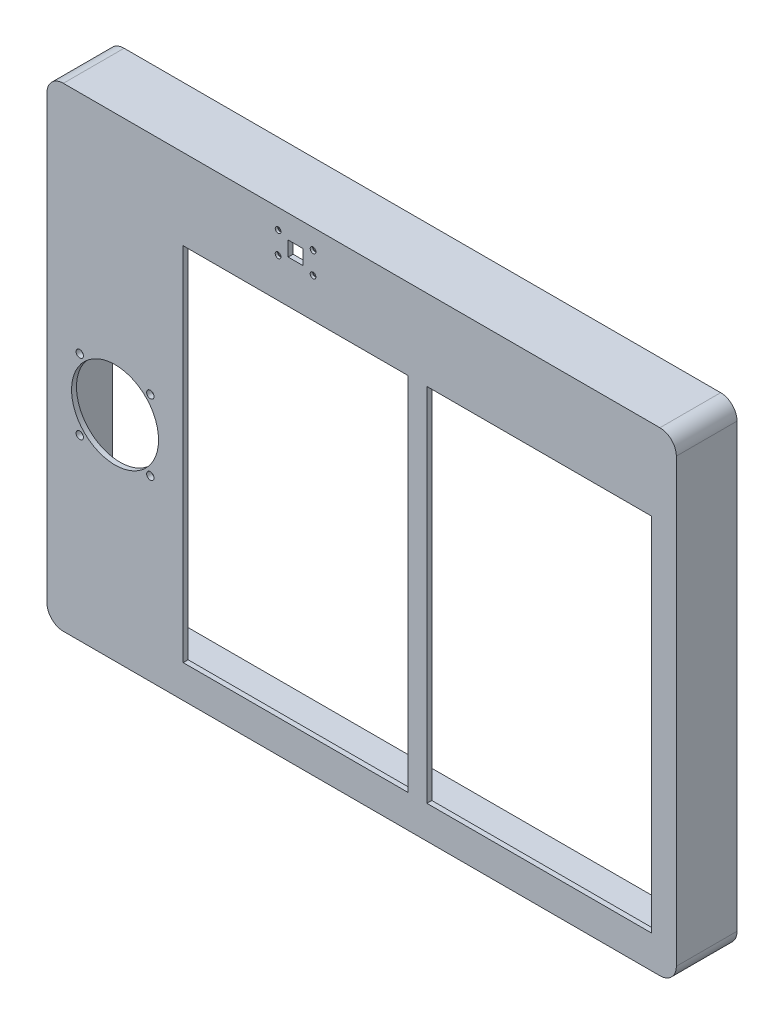
SolidWorks part; units mm, degrees
ref_plane "前视基准面" through (0, 0, 0) normal (0, 0, 1) x (1, 0, 0)
ref_plane "上视基准面" through (0, 0, 0) normal (0, 1, 0) x (1, 0, 0)
ref_plane "右视基准面" through (0, 0, 0) normal (1, 0, 0) x (0, 0, -1)
other "Configuration Table"
sketch "草图1" plane through (0, 0, 0) normal (0, 0, 1) x (1, 0, 0)
  line L0 (151.5, 0) -> (292.5, 0)
  line L1 (3, 0) -> (144, 0)
  line L2 (0, -3) -> (0, -237)
  line L3 (3, -240) -> (144, -240)
  line L4 (147, -3) -> (147, -237)
  line L5 (31.5, -60) -> (115.5, -60)
  line L6 (28.5, -63) -> (28.5, -177)
  line L7 (31.5, -180) -> (115.5, -180)
  line L8 (118.5, -63) -> (118.5, -177)
  line L9 (148.5, -3) -> (148.5, -237)
  line L10 (151.5, -240) -> (292.5, -240)
  line L11 (295.5, -3) -> (295.5, -237)
  line L12 (180, -60) -> (264, -60)
  line L13 (177, -63) -> (177, -177)
  line L14 (180, -180) -> (264, -180)
  line L15 (267, -63) -> (267, -177)
  line L17 (5, -10) -> (142, -10)
  line L18 (-65, -151.5) -> (-8, -151.5)
  line L19 (-68, -148.5) -> (-68, -91.5)
  line L20 (-65, -88.5) -> (-8, -88.5)
  line L21 (-5, -148.5) -> (-5, -91.5)
  line L22 (-68, -151.5) -> (-5, -88.5) construction
  line L23 (-68, -88.5) -> (-5, -151.5) construction
  line L24 (5, -10) -> (5, -230)
  line L25 (-68, 39.2) -> (295.5, 39.2)
  line L26 (-78, 29.2) -> (-78, -240)
  line L27 (-68, -250) -> (295.5, -250)
  line L28 (305.5, 29.2) -> (305.5, -240)
  line L29 (5, -230) -> (142, -230)
  line L30 (142, -10) -> (142, -230)
  line L31 (153.5, -10) -> (290.5, -10)
  line L32 (153.5, -10) -> (153.5, -230)
  line L33 (153.5, -230) -> (290.5, -230)
  line L34 (290.5, -10) -> (290.5, -230)
  line L42 (61.85, 29.2) -> (85.15, 29.2)
  line L43 (60.85, 28.2) -> (60.85, 6)
  line L44 (61.85, 5) -> (85.15, 5)
  line L45 (86.15, 28.2) -> (86.15, 6)
  line L46 (69, 25) -> (78, 25)
  line L47 (69, 25) -> (69, 16)
  line L48 (69, 16) -> (78, 16)
  line L49 (78, 25) -> (78, 16)
  circle A0 centre (6.75, -12.5) radius 1.5
  circle A1 centre (140.25, -12.5) radius 1.5
  circle A2 centre (140.25, -231) radius 1.5
  circle A3 centre (6.75, -231) radius 1.5
  arc A4 (0, -237) -> (3, -240) centre (3, -237) ccw
  arc A5 (144, -240) -> (147, -237) centre (144, -237) ccw
  arc A6 (144, 0) -> (147, -3) centre (144, -3) cw
  arc A7 (3, 0) -> (0, -3) centre (3, -3) ccw
  circle A8 centre (6.75, -12.5) radius 2.25
  circle A9 centre (140.25, -12.5) radius 2.25
  circle A10 centre (140.25, -231) radius 2.25
  circle A11 centre (6.75, -231) radius 2.25
  arc A12 (28.5, -177) -> (31.5, -180) centre (31.5, -177) ccw
  arc A13 (115.5, -180) -> (118.5, -177) centre (115.5, -177) ccw
  arc A14 (115.5, -60) -> (118.5, -63) centre (115.5, -63) cw
  arc A15 (31.5, -60) -> (28.5, -63) centre (31.5, -63) ccw
  circle A16 centre (155.25, -12.5) radius 1.5
  circle A17 centre (288.75, -12.5) radius 1.5
  circle A18 centre (288.75, -231) radius 1.5
  circle A19 centre (155.25, -231) radius 1.5
  arc A20 (148.5, -237) -> (151.5, -240) centre (151.5, -237) ccw
  arc A21 (292.5, -240) -> (295.5, -237) centre (292.5, -237) ccw
  arc A22 (292.5, 0) -> (295.5, -3) centre (292.5, -3) cw
  arc A23 (151.5, 0) -> (148.5, -3) centre (151.5, -3) ccw
  circle A24 centre (155.25, -12.5) radius 2.25
  circle A25 centre (288.75, -12.5) radius 2.25
  circle A26 centre (288.75, -231) radius 2.25
  circle A27 centre (155.25, -231) radius 2.25
  arc A28 (177, -177) -> (180, -180) centre (180, -177) ccw
  arc A29 (264, -180) -> (267, -177) centre (264, -177) ccw
  arc A30 (264, -60) -> (267, -63) centre (264, -63) cw
  arc A31 (180, -60) -> (177, -63) centre (180, -63) ccw
  circle A32 centre (-58, -98.5) radius 2.25
  circle A36 centre (-36.5, -120) radius 26.5
  arc A37 (-65, -151.5) -> (-68, -148.5) centre (-65, -148.5) cw
  arc A38 (-8, -151.5) -> (-5, -148.5) centre (-8, -148.5) ccw
  arc A39 (-8, -88.5) -> (-5, -91.5) centre (-8, -91.5) cw
  arc A40 (-68, -91.5) -> (-65, -88.5) centre (-65, -91.5) cw
  circle A41 centre (-15, -98.5) radius 2.25
  circle A42 centre (-15, -141.5) radius 2.25
  circle A43 centre (-58, -141.5) radius 2.25
  arc A44 (295.5, 39.2) -> (305.5, 29.2) centre (295.5, 29.2) cw
  arc A45 (295.5, -250) -> (305.5, -240) centre (295.5, -240) ccw
  arc A46 (-78, -240) -> (-68, -250) centre (-68, -240) ccw
  arc A47 (-68, 39.2) -> (-78, 29.2) centre (-68, 29.2) ccw
  circle A60 centre (62.85, 27.2) radius 1.25
  circle A61 centre (84.15, 27.2) radius 1.25
  circle A62 centre (84.15, 13.9) radius 1.25
  circle A63 centre (62.85, 13.9) radius 1.25
  arc A64 (61.85, 29.2) -> (60.85, 28.2) centre (61.85, 28.2) ccw
  arc A65 (85.15, 29.2) -> (86.15, 28.2) centre (85.15, 28.2) cw
  arc A66 (85.15, 5) -> (86.15, 6) centre (85.15, 6) ccw
  arc A67 (60.85, 6) -> (61.85, 5) centre (61.85, 6) ccw
  circle A68 centre (62.85, 27.2) radius 1.75
  circle A69 centre (84.15, 27.2) radius 1.75
  circle A70 centre (84.15, 13.9) radius 1.75
  circle A71 centre (62.85, 13.9) radius 1.75
  point P23 (0, 0)
  point P33 (-36.5, -120)
  point P38 (118.5, -180)
  point P41 (118.5, -60)
  point P44 (28.5, -60)
  dimension "D1" = 3
  dimension "D10" = 3
  dimension "D11" = 4.5
  dimension "D18" = 3
  dimension "D9" = 3
  dimension "D22" = 3
  dimension "D23" = 4.5
  dimension "D26" = 3
  dimension "D33" = 4.5
  dimension "D40" = 53
  dimension "D41" = 3
  dimension "D50" = 10
  dimension "D59" = 13.3
  dimension "D69" = 60.85
  dimension "D46" = 21.3
  dimension "D68" = 10
  dimension "D4" = 147
  dimension "D5" = 240
  dimension "D6" = 133.5
  dimension "D7" = 6.75
  dimension "D8" = 218.5
  dimension "D14" = 90
  dimension "D15" = 120
  dimension "D16" = 28.5
  dimension "D17" = 60
  dimension "D19" = 12.5
  dimension "D20" = 133.5
  dimension "D21" = 218.5
  dimension "D24" = 28.5
  dimension "D25" = 60
  dimension "D27" = 147
  dimension "D28" = 6.75
  dimension "D29" = 240
  dimension "D30" = 12.5
  dimension "D31" = 15
  dimension "D32" = 133.5
  dimension "D34" = 10
  dimension "D35" = 10
  dimension "D36" = 2
  dimension "D37" = 2
  dimension "D38" = 43
  dimension "D39" = 10
  dimension "D42" = 5
  dimension "D43" = 88.5
  dimension "D44" = 10
  dimension "D45" = 10
  dimension "D47" = 10
  dimension "D48" = 10
  dimension "D49" = 43
  dimension "D51" = 10
  dimension "D52" = 5
  dimension "D53" = 5
  dimension "D54" = 10
  dimension "D55" = 10
  dimension "D56" = 5
  dimension "D57" = 5
  dimension "D58" = 10
  dimension "D60" = 2
  dimension "D61" = 2
  dimension "D62" = 9
  dimension "D63" = 9
  dimension "D64" = 8.15
  dimension "D65" = 24.2
  dimension "D66" = 25.3
  dimension "D67" = 5
  dimension "D2" = 2
  dimension "D3" = 2
  dimension "D12" = 2
  dimension "D13" = 2
extrude "凸台-拉伸1" add sketch "草图1" against normal blind 37 contours L26 A46 L27 A45 L28 A44 L25 A47
shell "抽壳4" thickness 3 removed face at (113.75, -105.4, -37)
extrude "切除-拉伸8" cut sketch "草图1<8>" against normal blind 3 contours A32 | A41 | A42 | A43 | A36 | A60 | A61 | A62 | A63 | L17 L30 L29 L24 | L31 L34 L33 L32 | L47 L48 L49 L46
sketch "草图1<8>" plane through (0, 0, 0) normal (0, 0, 1) x (1, 0, 0) same geometry as "草图1"
extrude "切除-拉伸9" cut sketch "草图1<9>" against normal blind 1.5 contours A71 | A68 | A69 | A70
sketch "草图1<9>" plane through (0, 0, 0) normal (0, 0, 1) x (1, 0, 0) same geometry as "草图1"
sketch "草图2" plane through (-78, 0, 0) normal (-1, 0, 0) x (0, 0, 1)
  line L1 (-19.5, -100.8) -> (-18.5, -100.8)
  line L2 (-23, -104.3) -> (-23, -108.3)
  line L3 (-19.5, -111.8) -> (-18.5, -111.8)
  line L4 (-15, -104.3) -> (-15, -108.3)
  line L6 (-37, 39.2) -> (0, 39.2) construction
  line L8 (0, 29.2) -> (0, -240) construction
  arc A0 (-19.5, -100.8) -> (-23, -104.3) centre (-19.5, -104.3) ccw
  arc A1 (-23, -108.3) -> (-19.5, -111.8) centre (-19.5, -108.3) ccw
  arc A2 (-18.5, -111.8) -> (-15, -108.3) centre (-18.5, -108.3) ccw
  arc A3 (-18.5, -100.8) -> (-15, -104.3) centre (-18.5, -104.3) cw
  point P10 (-23, -100.8)
  point P15 (-15, -111.8)
  point P18 (-15, -100.8)
  dimension "D5" = 3.5
  dimension "D1" = 8
  dimension "D2" = 11
  dimension "D3" = 140
  dimension "D4" = 15
extrude "切除-拉伸10" cut sketch "草图2" against normal blind 3
